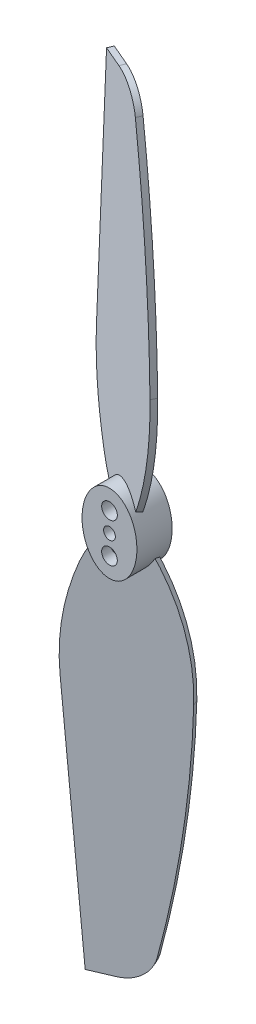
SolidWorks part; units mm, degrees
ref_plane "Front Plane" through (0, 0, 0) normal (1, 0, 0) x (0, 1, 0)
ref_plane "Top Plane" through (0, 0, 0) normal (0, 0, 1) x (0, 1, 0)
ref_plane "Right Plane" through (0, 0, 0) normal (0, 1, 0) x (-1, 0, 0)
sketch "Sketch1" plane through (0, 0, 0) normal (0, 0, 1) x (0, 1, 0)
  line L0 (0, 3.5) -> (0, -3.5)
  ellipse E0 centre (0, 0) end of major axis (-5, 0) minor radius 3.5 (0, -3.5) -> (0, 3.5) ccw
  dimension "D1" = 10
  dimension "D2" = 7
extrude "base cyl" add sketch "Sketch1" along normal blind 4.5
sketch "plane angle" plane through (0, 0, 0) normal (0, -1, 0) x (1, 0, 0)
  line L0 (-3.5, 0.75) -> (3.5, 3.75)
  line L1 (-3.5, 4.5) -> (-3.5, 0) construction
  line L2 (3.5, 4.5) -> (3.5, 0) construction
  line L3 (-3.5, 4.5) -> (3.5, 4.5) construction
  line L4 (-3.5, 0) -> (3.5, 0) construction
  line L5 (-3.5, 0.75) -> (-1.7002, 0.75) construction
  dimension "D1" = 0.75
  dimension "D2" = 0.75
  dimension "D3" = 23.199
ref_plane "Plane1" through (-0.8147, 0, 1.9009) normal (-0.3939, 0, 0.9191) x (0.9191, 0, 0.3939)
sketch "Sketch3" plane through (-0.8147, 0, 1.9009) normal (-0.3939, 0, 0.9191) x (0.9191, 0, 0.3939)
  line L0 (-1.4444, 0) -> (4.9896, 0) construction
  line L1 (-3.217, 0) -> (4.9896, 0) construction
  line L2 (0.8863, 0) -> (0.8863, 18) construction
  line L3 (7.3863, 18) -> (0.8863, 18) construction
  line L4 (-5.6137, 18) -> (-3.17, 50)
  line L5 (-0.17, 50) -> (-3.17, 50)
  line L6 (1.8863, 0) -> (-0.1137, 0)
  arc A0 (-3.7217, 5) -> (-5.6137, 18) centre (24.2992, 15.7157) cw
  arc A1 (-0.1137, 0) -> (-3.7217, 5) centre (7.4867, 9.2863) cw
  arc A2 (1.8863, 0) -> (7.3863, 18) centre (-22.6061, 17.3241) ccw
  arc A3 (7.3863, 18) -> (3.83, 46.8818) centre (-138.3433, 14.7157) ccw
  arc A4 (-0.17, 50) -> (3.83, 46.8818) centre (-0.0739, 45.9986) cw
  dimension "D1" = 6.5
  dimension "D5" = 30
  dimension "D4" = 30
  dimension "D6" = 12
  dimension "D13" = 4.0026
  dimension "D2" = 1
  dimension "D3" = 1
  dimension "D7" = 18
  dimension "D8" = 50
  dimension "D9" = 5
  dimension "D10" = 13
  dimension "D11" = 7
  dimension "D12" = 3
extrude "propeller 1" add sketch "Sketch3" along normal mid plane 0.75 separate body contours L4 L5 A4 A3 A2 L6 A1 A0
mirror "mirror propeller" about plane through (-3.5, 0, 4.5) normal (0, 1, 0) of bodies 103
move or copy body "flip rotation" bodies to move or copy 106 copy no rotation origin (0.2141, 0, 1.9998) rotation axis (0, 1, 0) rotation angle 46.397
mirror "mirror cyl" about plane through (-3.5, 0, 4.5) normal (0, 1, 0) of bodies 101
sketch "Sketch6" plane through (0, 0, 4.5) normal (0, 0, 1) x (1, 0, 0)
  line L0 (-3.5, 0) -> (3.5, 0) construction
  line L1 (0, 0) -> (0.4866, 0) construction
  circle A0 centre (0, 0) radius 0.75
  circle A1 centre (0, 2.5) radius 1
  circle A2 centre (0, -2.5) radius 1
  point P8 (0, 1.5)
  point P9 (0, -1.5)
  dimension "D1" = 1.5
  dimension "D2" = 2
  dimension "D3" = 3
extrude "holes" cut sketch "Sketch6" against normal through all
